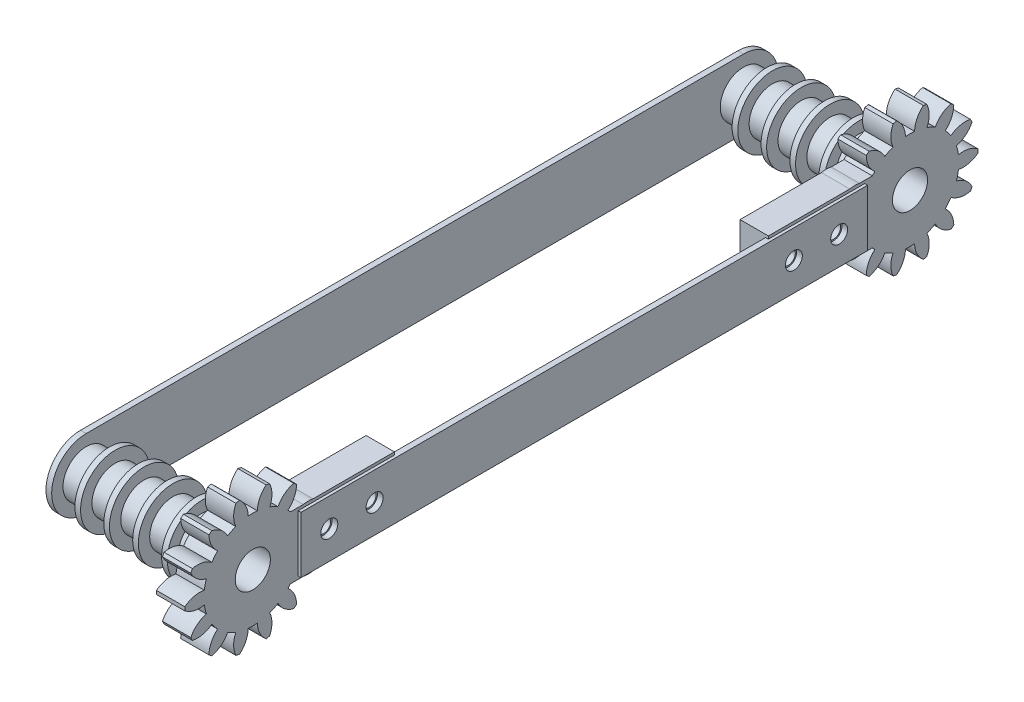
SolidWorks part; units mm, degrees
material "ABS"
ref_plane "Plane1" through (0, 0, 0) normal (0, 0, 1) x (1, 0, 0)
ref_plane "Plane2" through (0, 0, 0) normal (0, 1, 0) x (1, 0, 0)
ref_plane "Plane3" through (0, 0, 0) normal (1, 0, 0) x (0, 0, -1)
other "Configuration Table"
sketch "HoldingSke" plane through (0, 0, 0) normal (0, 1, 0) x (1, 0, 0)
  line L0 (0, 0) -> (0.6469, -0.1613)
  line L1 (-15, 0) -> (100, 0) construction
  line L2 (0, 0) -> (-2.1039, 2.3779)
  line L3 (0, 0) -> (-11.863, 4.5341)
  line L4 (0, 0) -> (8.3795, 2.0892)
  line L5 (0, 0) -> (-46.8476, -17.4728)
  line L6 (0, 0) -> (-4.1448, -2.7965)
  line L7 (-2.1039, 2.3779) -> (8.6586, 51.2059)
  line L8 (-76.2, 54.61) -> (-75.7, 54.61)
  line L9 (-71.009, 38.7566) -> (-53.1078, 45.2721)
  line L10 (-76.2, 71.12) -> (104.1128, 71.12)
  line L11 (0, 0) -> (-5, 0)
  line L12 (-76.2, 101.6) -> (-76.147, 101.6)
  line L13 (24.9733, 27.94) -> (52.9518, 28.4284)
  line L14 (24.9733, 27.94) -> (24.9743, 27.94)
  line L15 (24.9733, 27.94) -> (100.4006, 29.5858)
  line L16 (-63.627, -1.5) -> (-12.827, -1.5)
  circle A0 centre (0, 0) radius 1.5
  circle A1 centre (0, 0) radius 8.624
  circle A2 centre (0, 0) radius 37.5
  circle A3 centre (0, 0) radius 1.5
  dimension "Num_teeth" = 14
  dimension "Pitch_radius" = 180.3128
  dimension "Width" = 5
  dimension "Thickness" = 5
sketch "BasProSke" plane through (0, 0, 0) normal (0, 1, 0) x (1, 0, 0)
  line L0 (-10, 0) -> (60, 0) construction
  line L1 (0, 0) -> (0, 12)
  line L2 (0, 0) -> (5, 0)
  line L3 (5, 0) -> (5, 12)
  line L4 (5, 12) -> (0, 12)
  dimension "Thickness" = 5
  dimension "Diameter" = 24
revolve "Base-Revolve" add sketch "BasProSke" angle 360 about L0
sketch "TooCutSke" plane through (0, 0, 0) normal (1, 0, 0) x (0, 0, -1)
  line L1 (0, 0) -> (0, 107) construction
  line L2 (0, 0) -> (-1.2683, 10.4231) construction
  line L3 (0, 0) -> (-4.648, 20.3643) construction
  line L4 (-1.2683, 10.4231) -> (-2.324, 10.1822) construction
  arc A0 (0.8048, 8.5864) -> (-0.8048, 8.5864) centre (0, 0) ccw
  arc A1 (2.3844, 11.7866) -> (-2.3844, 11.7866) centre (0, 0) ccw
  circle A2 centre (0, 0) radius 10.5 construction
  circle A3 centre (0, 0) radius 9.8668 construction
  arc A4 (-0.8048, 8.5864) -> (-2.3844, 11.7866) centre (-5.004, 8.5037) ccw
  arc A5 (2.3844, 11.7866) -> (0.8048, 8.5864) centre (5.004, 8.5037) ccw
extrude "ToothCut" cut sketch "TooCutSke" along normal through all
fillet "Breaks" [suppressed] radius 0.03 tangent propagation no
fillet "RootFillets" [suppressed] radius 0.376
pattern_circular "TeethCuts" count 14 every 25.714 about axis through (-10, 0, 0) along (1, 0, 0) of "ToothCut", "RootFillets", "Breaks"
sketch "HubNeaOneSke" plane through (0, 0, 0) normal (-1, 0, 0) x (0, 0, 1)
  circle A0 centre (0, 0) radius 8.624
  dimension "Diameter" = 17.248
extrude "HubNearOne" [suppressed] add sketch "HubNeaOneSke" along normal blind 45.0001
sketch "HubNeaBotSke" plane through (0, 0, 0) normal (-1, 0, 0) x (0, 0, 1)
  circle A0 centre (0, 0) radius 8.624
  dimension "Diameter" = 17.248
extrude "HubNearBoth" [suppressed] add sketch "HubNeaBotSke" along normal blind 22.5
ref_plane "FarPln" through (5, 0, 0) normal (1, 0, 0) x (0, 0, -1)
sketch "HubFarSke" plane through (5, 0, 0) normal (1, 0, 0) x (0, 0, -1)
  circle A0 centre (0, 0) radius 8.624
  dimension "Diameter" = 17.248
extrude "HubFar" [suppressed] add sketch "HubFarSke" along normal blind 22.5
sketch "BorSke" plane through (0, 0, 0) normal (1, 0, 0) x (0, 0, -1)
  circle A0 centre (0, 0) radius 3.1
  dimension "Diameter" = 6.2
extrude "Bore" cut sketch "BorSke" along normal mid plane 100.0001
sketch "KeySke" plane through (0, 0, 0) normal (1, 0, 0) x (0, 0, -1)
  line L0 (-0.6, 0) -> (-0.6, 2)
  line L1 (-0.6, 2) -> (0.6, 2)
  line L2 (0.6, 2) -> (0.6, 0)
  line L3 (0, 0) -> (0, 34) construction
  line L4 (-0.6, 0) -> (0.6, 0)
  dimension "Width" = 1.2
extrude "Keyway" [suppressed] cut sketch "KeySke" along normal mid plane 100.0001
pattern_circular "Keyway2" [suppressed] count 2 every 90 about axis through (-10, 0, 0) along (1, 0, 0) reverse direction yes
sketch "ｽｹｯﾁ2" plane through (5, 0, 0) normal (1, 0, 0) x (0, 0, -1)
  line L0 (5, 5.5) -> (5, -5.5)
  line L1 (5, -5.5) -> (25, -5.5)
  line L2 (25, -5.5) -> (25, 5.5)
  line L3 (25, 5.5) -> (5, 5.5)
  line L4 (0, 0) -> (5, 0) construction
  dimension "D1" = 11
  dimension "D2" = 5
  dimension "D3" = 20
extrude "ﾎﾞｽ - 押し出し1" add sketch "ｽｹｯﾁ2" against normal up to surface (5 mm away) up to face at (0, 0, -3.1)
sketch "ｽｹｯﾁ3" plane through (5, 0, 0) normal (1, 0, 0) x (0, 0, -1)
  line L0 (25, -5.5) -> (25, 5.5) construction
  line L1 (25, -5) -> (8, -5)
  line L2 (25, -5) -> (25, 5)
  line L3 (25, 5) -> (8, 5)
  line L4 (8, -5) -> (8, 5)
  line L5 (8, 0) -> (0, 0) construction
  dimension "D1" = 10
  dimension "D2" = 8
extrude "ｶｯﾄ - 押し出し1" cut sketch "ｽｹｯﾁ3" against normal blind 0.5
sketch "ｽｹｯﾁ5" plane through (0, 0, -8) normal (0, 0, -1) x (-1, 0, 0)
  line L0 (-4.5, 5) -> (-5, 5) construction
  line L1 (-4.5, -5) -> (-14.5, -5)
  line L2 (-4.5, -5) -> (-4.5, 5)
  line L3 (-4.5, 5) -> (-14.5, 5)
  line L4 (-14.5, -5) -> (-14.5, 5)
  line L5 (-5.5, -4) -> (-5.5, 4)
  line L6 (-5.5, 4) -> (-13.5, 4)
  line L7 (-13.5, -4) -> (-13.5, 4)
  line L8 (-5.5, -4) -> (-13.5, -4)
  dimension "D1" = 1
extrude "ﾎﾞｽ - 押し出し2" add sketch "ｽｹｯﾁ5" along normal blind 100 separate body
sketch "ｽｹｯﾁ4" plane through (0, 0, 0) normal (-1, 0, 0) x (0, 0, 1)
  line L0 (0, 0) -> (-25, 0) construction
  line L1 (-25, 5.5) -> (-25, -5.5) construction
  line L2 (-8, 5) -> (-8, -5) construction
  circle A0 centre (-21, 0) radius 1.25
  circle A1 centre (-13, 0) radius 1.25
  dimension "D3" = 2.5
  dimension "D1" = 5
  dimension "D2" = 8
extrude "ｶｯﾄ - 押し出し2" cut sketch "ｽｹｯﾁ4" against normal through all and the other way through all
sketch "ｽｹｯﾁ7" plane through (0, 0, 0) normal (-1, 0, 0) x (0, 0, 1)
  circle A0 centre (0, 0) radius 4.1
  circle A1 centre (0, 0) radius 3.1
  circle A2 centre (0, 0) radius 3.1 construction
  dimension "D2" = 8.2
extrude "ﾎﾞｽ - 押し出し3" add sketch "ｽｹｯﾁ7" along normal blind 4 separate body
sketch "ｽｹｯﾁ9" plane through (-4, 0, 0) normal (-1, 0, 0) x (0, 0, 1)
  circle A0 centre (0, 0) radius 3.1 construction
  circle A1 centre (0, 0) radius 3.1
  circle A2 centre (0, 0) radius 6.1
  circle A3 centre (0, 0) radius 4.1 construction
  dimension "D1" = 2
extrude "ﾎﾞｽ - 押し出し4" add sketch "ｽｹｯﾁ9" along normal blind 1 separate body
ref_plane "平面1" through (0, 0, -58) normal (0, 0, -1) x (-1, 0, 0)
mirror "ﾐﾗｰ2" about plane through (0, 0, -58) normal (0, 0, -1) of bodies 106 111 121
sketch "ｽｹｯﾁ6" plane through (4.5, 0, 0) normal (-1, 0, 0) x (0, 0, 1)
  circle A0 centre (-103, 0) radius 1.5
  circle A1 centre (-95, 0) radius 1.5
  circle A2 centre (-21, 0) radius 1.5
  circle A3 centre (-13, 0) radius 1.5
  dimension "D1" = 3
extrude "ｶｯﾄ - 押し出し3" cut sketch "ｽｹｯﾁ6" against normal through all
pattern_linear "直線ﾊﾟﾀｰﾝ1" count 5 spacing 5.1 along (-1, 0, 0) of bodies 112 111
pattern_linear "直線ﾊﾟﾀｰﾝ2" count 4 spacing 5.1 along (-1, 0, 0) of bodies 121 122
sketch "ｽｹｯﾁ10" plane through (0, 0, -8) normal (0, 0, 1) x (1, 0, 0)
  line L0 (14.5, -5) -> (4.5, -5) construction
  line L1 (5.5, -5) -> (14.5, -5)
  line L2 (5.5, -5) -> (5.5, 5)
  line L3 (5.5, 5) -> (14.5, 5)
  line L4 (14.5, -5) -> (14.5, 5)
  line L6 (5.5, -4) -> (5.5, 4) construction
extrude "ｶｯﾄ - 押し出し4" cut sketch "ｽｹｯﾁ10" against normal up to surface (100 mm away) up to face at (9.5, 0, -108)
sketch "ｽｹｯﾁ12" plane through (-24.4, 0, 0) normal (-1, 0, 0) x (0, 0, 1)
  line L0 (0, 0) -> (-116, 0) construction
  line L1 (0, -6.1) -> (-116, -6.1)
  line L2 (0, 6.1) -> (-116, 6.1)
  arc A0 (0, -6.1) -> (0, 6.1) centre (0, 0) ccw
  arc A1 (-116, 6.1) -> (-116, -6.1) centre (-116, 0) ccw
  circle A2 centre (-116, 0) radius 6.1 construction
  circle A3 centre (0, 0) radius 3.1 construction
  circle A4 centre (-116, 0) radius 3.1 construction
  circle A5 centre (0, 0) radius 3.1
  circle A6 centre (-116, 0) radius 3.1
  point P4 (-58, 0)
extrude "ﾎﾞｽ - 押し出し5" add sketch "ｽｹｯﾁ12" along normal blind 1 separate body
equation "' \"Module@HoldingSke\" = 6.35"
equation "' \"Num_teeth@HoldingSke\" = 12"
equation "' \"Ap@HoldingSke\" =  20"
equation "' \"Ap@HoldingSke\" = 20"
equation "' \"Width@HoldingSke\" = 0.5 * 25.4"
equation "' \"Hub_dia@HoldingSke\"= 1 * 25.4"
equation "' \"Hub_dia@HoldingSke\" = 1 * 25.4"
equation "' \"Overall_len@HoldingSke\" = 1.0 * 25.4"
equation "' \"Bore@HoldingSke\" = 0.75 * 25.4"
equation "' \"T_dim@HoldingSke\" = 0.1 * 25.4"
equation "' \"Width@KeySke\" = 0.25 * 25.4"
equation "' \"Show_teeth@HoldingSke\" = 13"
equation "' \"Backlash@HoldingSke\" = 0.009 * 25.4"
equation "' \"Addendum_fac@HoldingSke\" = 1.0"
equation "' \"Dedendum_fac@HoldingSke\" = 1.25"
equation "' \"Dedendum_add@HoldingSke\" = 0.00005 * 25.4"
equation "' \"Clearance_fac@HoldingSke\" = 0.25"
equation "\"Pitch@HoldingSke\" = 1 / \"Module@HoldingSke\""
equation "\"Overcut_dia@TooCutSke\" = (\"Num_teeth@HoldingSke\" + 2 * \"Addendum_fac@HoldingSke\") / \"Pitch@HoldingSke\" + 0.002 * 25.4"
equation "\"Pitch_dia@TooCutSke\" = \"Num_teeth@HoldingSke\" / \"Pitch@HoldingSke\""
equation "\"Base_dia@TooCutSke\" = \"Num_teeth@HoldingSke\" / \"Pitch@HoldingSke\" * cos((\"Ap@HoldingSke\"  * 3.14159265 / 180))"
equation "\"Root_dia@TooCutSke\" = (\"Num_teeth@HoldingSke\" + 2) / \"Pitch@HoldingSke\" - 2 * (\"Addendum_fac@HoldingSke\" + \"Dedendum_fac@HoldingSke\") / \"Pitch@HoldingSke\" - \"Dedendum_add@HoldingSke\" * 2"
equation "\"Half_ang@TooCutSke\" = 180 / \"Num_teeth@HoldingSke\""
equation "\"Half_CT@TooCutSke\" = \"Num_teeth@HoldingSke\" / \"Pitch@HoldingSke\" * sin((3.14159265 / 2 / \"Num_teeth@HoldingSke\")) / 2 - 7 * \"Backlash@HoldingSke\" / 4"
equation "\"Flank_rad@TooCutSke\" = \"Num_teeth@HoldingSke\" / \"Pitch@HoldingSke\" / 5"
equation "\"Radius@RootFillets\" = \"Clearance_fac@HoldingSke\" / \"Pitch@HoldingSke\" + \"Dedendum_add@HoldingSke\""
equation "\"Break_rad@Breaks\" = 0.02 / \"Pitch@HoldingSke\""
equation "\"Thickness@HoldingSke\" = \"Width@HoldingSke\""
equation "\"OAL@HoldingSke\" = \"Thickness@HoldingSke\""
equation "\"MHD@HoldingSke\" = (\"Num_teeth@HoldingSke\" + 2) / \"Pitch@HoldingSke\" - 2 * (\"Addendum_fac@HoldingSke\" + \"Dedendum_fac@HoldingSke\")  / \"Pitch@HoldingSke\" - \"Dedendum_add@HoldingSke\" * 2"
equation "\"MBD@HoldingSke\" = (\"Num_teeth@HoldingSke\" + 2) / \"Pitch@HoldingSke\" - 2 * (\"Addendum_fac@HoldingSke\" + \"Dedendum_fac@HoldingSke\")  / \"Pitch@HoldingSke\" - \"Dedendum_add@HoldingSke\" * 2 - 0.002 * 25.4"
equation "\"MHD@HoldingSke\" = ((sgn( \"MHD@HoldingSke\" - \"Hub_dia@HoldingSke\" )-1)*( \"MHD@HoldingSke\" - \"Hub_dia@HoldingSke\" ))/-2+ \"Hub_dia@HoldingSke\""
equation "\"MBD@HoldingSke\" = ((sgn( \"MBD@HoldingSke\" - \"Bore@HoldingSke\" )-1)*( \"MBD@HoldingSke\" - \"Bore@HoldingSke\" ))/-2+ \"Bore@HoldingSke\""
equation "\"OAL@HoldingSke\" = ((sgn( \"OAL@HoldingSke\" - \"Overall_len@HoldingSke\" )+1)*( \"OAL@HoldingSke\" - \"Overall_len@HoldingSke\" ))/2 + \"Overall_len@HoldingSke\" + 0.000002 * 25.4"
equation "\"Num_teeth@TeethCuts\" = int( \"Show_teeth@HoldingSke\" ) + 1"
equation "\"Num_teeth@TeethCuts\" = ((sgn( \"Num_teeth@TeethCuts\" - \"Num_teeth@HoldingSke\" )-1)*( \"Num_teeth@TeethCuts\" - \"Num_teeth@HoldingSke\" ))/-2+ \"Num_teeth@HoldingSke\""
equation "\"Num_teeth@TeethCuts\" = ((sgn( \"Num_teeth@TeethCuts\" - 2.0)+1)*( \"Num_teeth@TeethCuts\" - 2.0))/2 +2.0"
equation "\"Angle@TeethCuts\" = 360.0 / \"Num_teeth@HoldingSke\""
equation "\"Diameter@BasProSke\" = (\"Num_teeth@HoldingSke\" + 2 * \"Addendum_fac@HoldingSke\") / \"Pitch@HoldingSke\""
equation "\"Thickness@BasProSke\"  = \"Thickness@HoldingSke\""
equation "' \"Fillet_rad@BasProSke\" =  \"Thickness@HoldingSke\" * 0.05"
equation "' \"Fillet_rad@BasProSke\" = \"Thickness@HoldingSke\" * 0.05"
equation "\"MHD@HoldingSke\" = ((sgn( \"MHD@HoldingSke\" - \"Root_dia@TooCutSke\" )-1)*( \"MHD@HoldingSke\" - \"Root_dia@TooCutSke\" ))/-2+ \"Root_dia@TooCutSke\""
equation "\"Diameter@HubNeaOneSke\" = \"MHD@HoldingSke\""
equation "\"Length@HubNearOne\" = \"OAL@HoldingSke\" - \"Thickness@BasProSke\""
equation "\"Diameter@HubNeaBotSke\" = \"MHD@HoldingSke\""
equation "\"Length@HubNearBoth\" = ( \"OAL@HoldingSke\" - \"Thickness@BasProSke\" ) / 2.0"
equation "\"Thickness@FarPln\" = \"Thickness@BasProSke\""
equation "\"Diameter@HubFarSke\" = \"MHD@HoldingSke\""
equation "\"Length@HubFar\" = ( \"OAL@HoldingSke\" - \"Thickness@BasProSke\" ) / 2.0"
equation "\"D1@Bore\" = \"OAL@HoldingSke\" * 2.0"
equation "\"D1@Keyway\" = \"OAL@HoldingSke\" * 2.0"
equation "\"Offset@KeySke\" = \"T_dim@HoldingSke\" + \"MBD@HoldingSke\" / 2.0"
